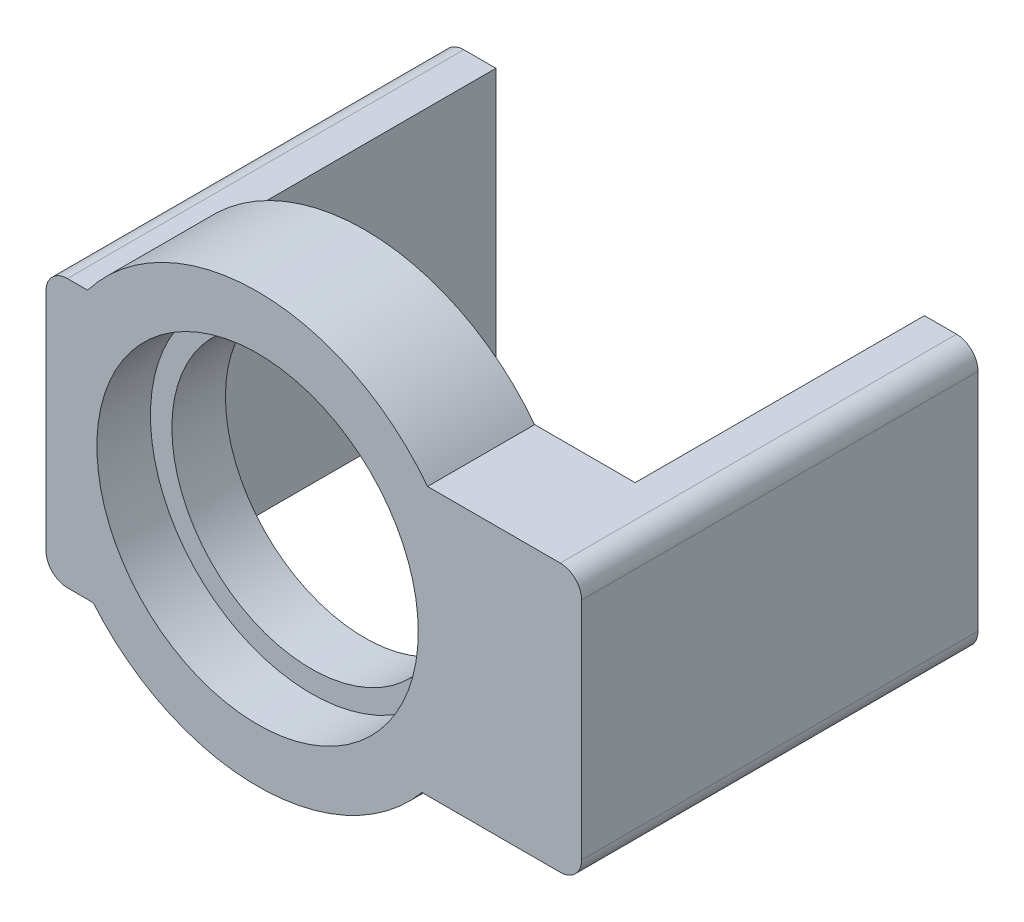
SolidWorks part; units mm, degrees
ref_plane "Front Plane" through (0, 0, 0) normal (0, 0, 1) x (1, 0, 0)
ref_plane "Top Plane" through (0, 0, 0) normal (0, 1, 0) x (1, 0, 0)
ref_plane "Right Plane" through (0, 0, 0) normal (1, 0, 0) x (0, 0, -1)
sketch "Sketch2" plane through (0, 0, 1.8) normal (0, 0, 1) x (1, 0, 0)
  line L5 (-76.5966, -98.699) -> (-81, -98.699)
  line L6 (-77.1172, -73.699) -> (-81, -73.699)
  line L9 (-31, -73.699) -> (-45.3828, -73.699)
  line L10 (-31, -98.699) -> (-45.9034, -98.699)
  line L14 (-31, -73.699) -> (-31, -98.699)
  line L16 (-81, -98.699) -> (-81, -73.699)
  circle A1 centre (-61.25, -85.874) radius 15
  arc A2 (-76.5966, -98.699) -> (-45.9034, -98.699) centre (-61.25, -85.874) ccw
  arc A4 (-45.3828, -73.699) -> (-77.1172, -73.699) centre (-61.25, -85.874) ccw
  point P6 (0, 0)
  point P8 (0, 0)
  point P9 (0, 0)
  point P15 (0, 0)
  point P17 (0, 0)
  point P19 (0, 0)
  point P21 (0, 0)
  point P22 (0, 0)
  point P23 (0, 0)
  point P24 (0, 0)
  point P25 (0, 0)
extrude "Boss-Extrude1" add sketch "Sketch2" against normal blind 5
sketch "Sketch3" plane through (0, 0, -3.2) normal (0, 0, -1) x (-1, 0, 0)
  line L3 (76.5966, -98.699) -> (81, -98.699)
  line L4 (76.5966, -98.699) -> (81, -98.699)
  line L5 (31, -73.699) -> (31, -98.699)
  line L14 (81, -73.699) -> (77.1172, -73.699)
  line L15 (81, -73.699) -> (77.1172, -73.699)
  line L16 (45.3828, -73.699) -> (31, -73.699)
  line L17 (45.3828, -73.699) -> (31, -73.699)
  line L18 (31, -73.699) -> (31, -98.699)
  line L20 (31, -98.699) -> (45.9034, -98.699)
  line L21 (31, -98.699) -> (45.9034, -98.699)
  line L22 (81, -98.699) -> (81, -73.699)
  line L23 (81, -98.699) -> (81, -73.699)
  arc A1 (45.9034, -98.699) -> (76.5966, -98.699) centre (61.25, -85.874) ccw
  arc A2 (45.9034, -98.699) -> (76.5966, -98.699) centre (61.25, -85.874) ccw
  circle A3 centre (61.25, -85.874) radius 13
  arc A6 (77.1172, -73.699) -> (45.3828, -73.699) centre (61.25, -85.874) ccw
  arc A8 (77.1172, -73.699) -> (45.3828, -73.699) centre (61.25, -85.874) ccw
  dimension "D1" = 0
extrude "Boss-Extrude2" add sketch "Sketch3" along normal blind 5
sketch "Sketch6" plane through (0, 0, -8.2) normal (0, 0, -1) x (-1, 0, 0)
  line L0 (81, -73.699) -> (77.1172, -73.699) construction
  line L1 (31, -98.699) -> (36, -98.699)
  line L2 (31, -98.699) -> (31, -73.699)
  line L3 (31, -73.699) -> (36, -73.699)
  line L4 (36, -98.699) -> (36, -73.699)
  line L5 (81, -98.699) -> (76, -98.699)
  line L6 (81, -98.699) -> (81, -73.699)
  line L7 (81, -73.699) -> (76, -73.699)
  line L8 (76, -98.699) -> (76, -73.699)
  line L9 (45.3828, -73.699) -> (31, -73.699) construction
  point P10 (0, 0)
  point P13 (0, 0)
  point P14 (0, 0)
extrude "Boss-Extrude3" add sketch "Sketch6" along normal up to surface (27 mm away)
fillet "Fillet1" radius 2 4 edges at (-31, -73.699, -16.7) (-31, -98.699, -16.7) (-81, -73.699, -16.7) (-81, -98.699, -16.7)
